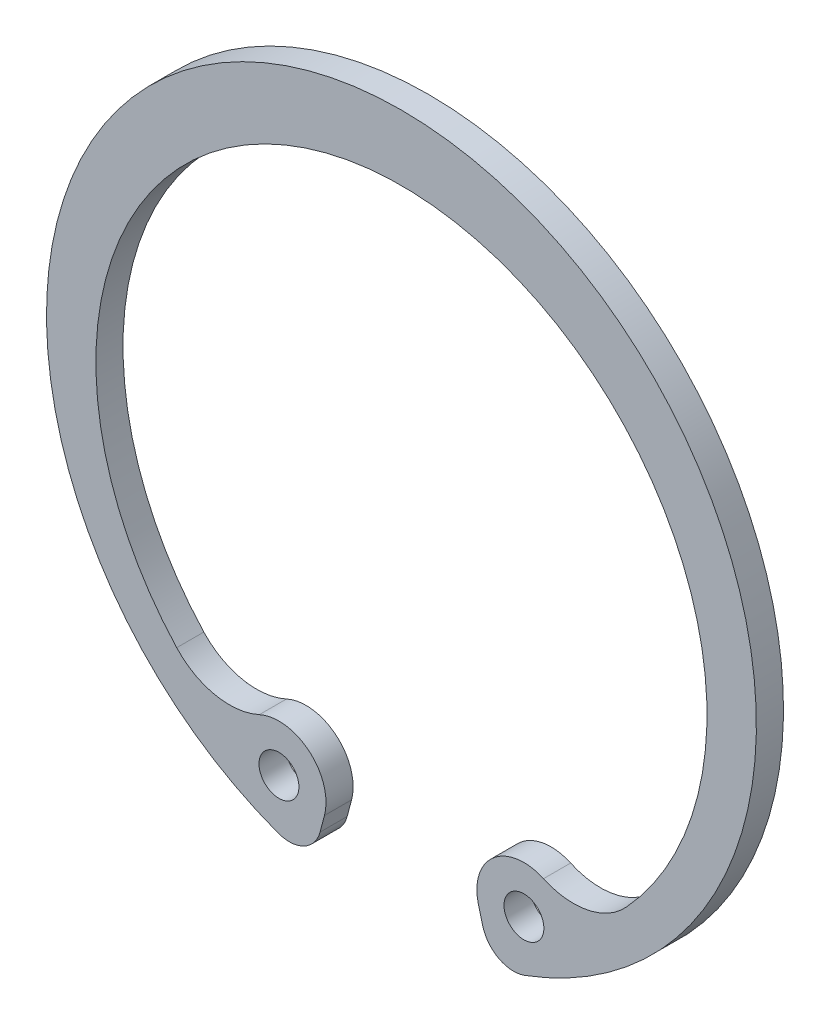
SolidWorks part; units mm, degrees
material "AISI 1020"
ref_plane "Спереди" through (0, 0, 0) normal (0, 0, 1) x (1, 0, 0)
ref_plane "Сверху" through (0, 0, 0) normal (0, 1, 0) x (1, 0, 0)
ref_plane "Справа" through (0, 0, 0) normal (1, 0, 0) x (0, 0, -1)
sketch "Эскиз1" plane through (0, 0, 0) normal (0, 0, 1) x (1, 0, 0)
  line L0 (0, -1000) -> (0, 49000) construction
  line L1 (0, 0) -> (8.95, -17.6618) construction
  line L2 (6.1493, -18.5883) -> (6.4867, -19.6083)
  line L3 (0, 18.65) -> (39.3, 18.65) construction
  arc A0 (9.1938, -20.8096) -> (0, 22.75) centre (0, 0) ccw
  circle A2 centre (8.95, -17.6618) radius 1.25
  arc A3 (10.0108, -14.9091) -> (6.1493, -18.5883) centre (8.95, -17.6618) ccw
  arc A4 (10.0108, -14.9091) -> (15.0833, -13.5943) centre (11.6291, -10.7101) ccw
  arc A5 (6.4867, -19.6083) -> (9.1938, -20.8096) centre (8.3855, -18.9801) ccw
  arc A6 (15.0833, -13.5943) -> (0, 18.65) centre (0, -1) ccw
  dimension "_d4" = 2.5
  dimension "_r1" = 4.5
  dimension "_r2" = 2
  dimension "D1" = 22
sketch "Эскиз2" plane through (0, 0, 0) normal (0, 0, 1) x (1, 0, 0)
  line L0 (0, -201000) -> (0, 249000) construction
  line L1 (-5.1006, -19.4997) -> (-4.8263, -18.461)
  line L2 (6.1493, -18.5883) -> (6.4867, -19.6083) construction
  line L3 (0, 0) -> (9.1938, -20.8096) construction
  line L4 (0, 0) -> (-7.7291, -20.8644) construction
  line L5 (6.4867, -19.6083) -> (9.1938, -20.8096) construction
  line L6 (-7.7291, -20.8644) -> (-5.1006, -19.4997) construction
  line L7 (10.0108, -14.9091) -> (6.1493, -18.5883) construction
  line L8 (-8.9058, -15.025) -> (-4.8263, -18.461) construction
  line L9 (0, 22.25) -> (0, 23.95) construction
  circle A0 centre (0, 0) radius 22.25 construction
  circle A1 centre (0, 0) radius 21 construction
  circle A2 centre (0, 0) radius 14.6 construction
  arc A3 (0, 22.25) -> (-7.7291, -20.8644) centre (0, 0) ccw
  arc A4 (0, 18.15) -> (-14.0877, -13.9819) centre (0, -1.0042) ccw
  arc A5 (-7.7291, -20.8644) -> (-5.1006, -19.4997) centre (-7.0343, -18.989) ccw
  arc A6 (-4.8263, -18.461) -> (-8.9058, -15.025) centre (-7.6784, -17.7076) ccw
  arc A7 (6.4867, -19.6083) -> (9.1938, -20.8096) centre (8.3855, -18.9801) ccw construction
  arc A8 (10.0108, -14.9091) -> (6.1493, -18.5883) centre (8.95, -17.6618) ccw construction
  arc A9 (-14.0877, -13.9819) -> (-8.9058, -15.025) centre (-10.778, -10.933) ccw
  circle A10 centre (-7.6784, -17.7076) radius 1.25
  circle A11 centre (8.95, -17.6618) radius 1.25 construction
  arc A13 (10.0108, -14.9091) -> (15.0833, -13.5943) centre (11.6291, -10.7101) ccw construction
  dimension "D3" = 159.38
  dimension "_s" = 1.7
sketch "Эскиз3" plane through (0, 0, 0) normal (0, 0, 1) x (1, 0, 0)
  line L0 (-5.1006, -19.4997) -> (-4.8263, -18.461) construction
  line L1 (-5.1006, -19.4997) -> (-4.8263, -18.461)
  line L2 (0, -1000) -> (0, 49000) construction
  line L3 (0, -1000.0733) -> (0, 48999.9267) construction
  line L4 (5.1006, -19.4997) -> (4.8263, -18.461)
  arc A0 (0, 18.15) -> (-14.0877, -13.9819) centre (0, -1.0042) ccw construction
  arc A1 (-14.0877, -13.9819) -> (-8.9058, -15.025) centre (-10.778, -10.933) ccw construction
  arc A2 (-4.8263, -18.461) -> (-8.9058, -15.025) centre (-7.6784, -17.7076) ccw construction
  arc A3 (-7.7291, -20.8644) -> (-5.1006, -19.4997) centre (-7.0343, -18.989) ccw construction
  arc A4 (0, 22.25) -> (-7.7291, -20.8644) centre (0, 0) ccw construction
  arc A5 (14.0877, -13.9819) -> (-14.0877, -13.9819) centre (0, -1.0042) ccw
  arc A6 (-14.0877, -13.9819) -> (-8.9058, -15.025) centre (-10.778, -10.933) ccw
  arc A7 (-4.8263, -18.461) -> (-8.9058, -15.025) centre (-7.6784, -17.7076) ccw
  arc A8 (-7.7291, -20.8644) -> (-5.1006, -19.4997) centre (-7.0343, -18.989) ccw
  arc A9 (7.7291, -20.8644) -> (-7.7291, -20.8644) centre (0, 0) ccw
  circle A10 centre (-7.6784, -17.7076) radius 1.25 construction
  circle A11 centre (-7.6784, -17.7076) radius 1.25
  circle A12 centre (7.6784, -17.7076) radius 1.25
  arc A13 (14.0877, -13.9819) -> (8.9058, -15.025) centre (10.778, -10.933) cw
  arc A14 (4.8263, -18.461) -> (8.9058, -15.025) centre (7.6784, -17.7076) cw
  arc A15 (7.7291, -20.8644) -> (5.1006, -19.4997) centre (7.0343, -18.989) cw
extrude "Бобышка-Вытянуть1" add sketch "Эскиз3" along normal blind 1.7
equation "\"D1@Эскиз1\"=\"_d3@Эскиз1\"/2"
equation "\"D3@Эскиз2\"=(\"D2@Эскиз2\"*2*\"D1@Эскиз2\"/360)/(\"_d1@Эскиз2\"/360)"
equation "\"D1@Бобышка-Вытянуть1\"= \"_s@Эскиз2\""
